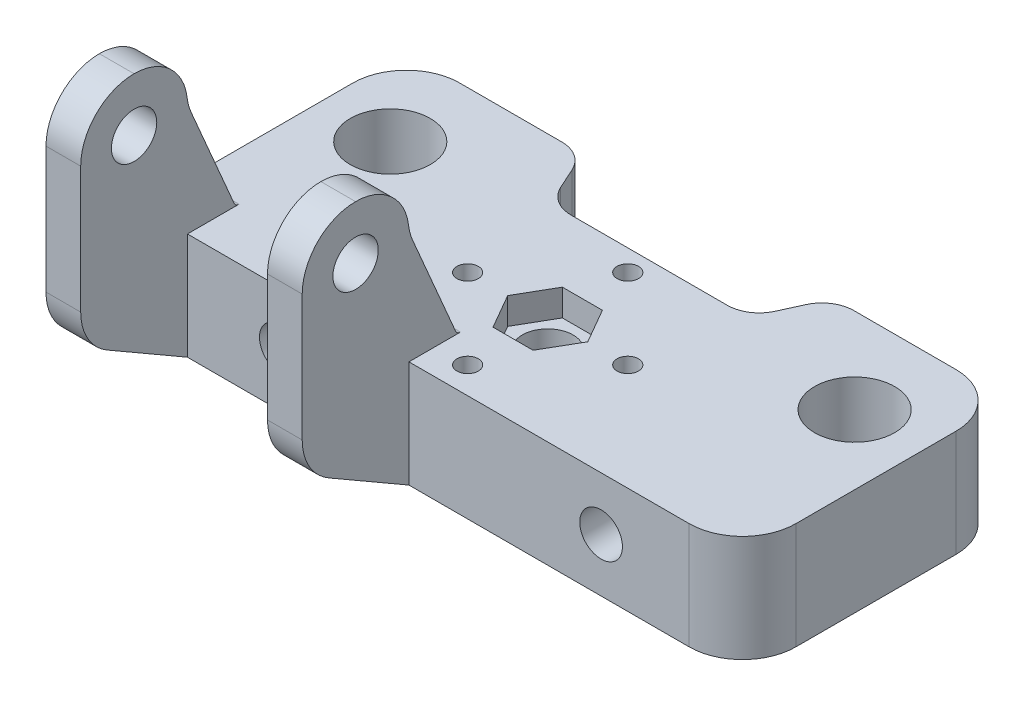
SolidWorks part; units mm, degrees
material "ABS PC"
ref_plane "Front Plane" through (0, 0, 0) normal (0, 0, 1) x (1, 0, 0)
ref_plane "Top Plane" through (0, 0, 0) normal (0, 1, 0) x (1, 0, 0)
ref_plane "Right Plane" through (0, 0, 0) normal (1, 0, 0) x (0, 0, -1)
sketch "Sketch1" plane through (0, 0, 0) normal (0, 1, 0) x (1, 0, 0)
  line L0 (56.5, 0) -> (-56.5, 0)
  line L1 (56.5, 0) -> (56.5, 50)
  line L2 (-56.5, 0) -> (-56.5, 50)
  line L3 (56.5, 50) -> (-56.5, 50)
  dimension "D1" = 113
  dimension "D2" = 50
extrude "Boss-Extrude1" add sketch "Sketch1" along normal blind 20
sketch "Sketch2" plane through (0, 20, 0) normal (0, 1, 0) x (1, 0, 0)
  line L1 (56.5, 0) -> (56.5, 50) construction
  line L3 (56.5, 50) -> (-56.5, 50) construction
  circle A0 centre (-43.5, 34) radius 7.5
  circle A1 centre (43.5, 34) radius 7.5
  circle A2 centre (0, 20) radius 4.75
  circle A3 centre (15, 20) radius 2
  circle A4 centre (-15, 20) radius 2
  circle A5 centre (0, 35) radius 2
  circle A6 centre (0, 5) radius 2
  dimension "D2" = 56.5
  dimension "D3" = 30
  dimension "D5" = 15
  dimension "D6" = 15
  dimension "D1" = 43.5
  dimension "D4" = 43.5
  dimension "D7" = 14
  dimension "D8" = 9.5
  dimension "D9" = 15
  dimension "D10" = 15
  dimension "D11" = 4
  dimension "D12" = 15
  dimension "D13" = 15
extrude "Cut-Extrude1" cut sketch "Sketch2" against normal through all
sketch "Sketch3" plane through (0, 20, 0) normal (0, 1, 0) x (1, 0, 0)
  line L1 (-3.75, 13.5048) -> (3.75, 13.5048)
  line L2 (3.75, 13.5048) -> (7.5, 20)
  line L3 (7.5, 20) -> (3.75, 26.4952)
  line L4 (3.75, 26.4952) -> (-3.75, 26.4952)
  line L5 (-3.75, 26.4952) -> (-7.5, 20)
  line L6 (-7.5, 20) -> (-3.75, 13.5048)
  circle A0 centre (0, 20) radius 6.4952 construction
  circle A1 centre (0, 20) radius 4.75 construction
  dimension "D1" = 15
extrude "Cut-Extrude2" cut sketch "Sketch3" against normal blind 5
sketch "Sketch5" plane through (0, 0, -50) normal (0, 0, -1) x (-1, 0, 0)
  line L3 (-56.5, 20) -> (-56.5, 0) construction
  line L4 (-56.5, 0) -> (56.5, 0) construction
  circle A0 centre (30, 10) radius 4
  circle A1 centre (-30, 10) radius 4
  dimension "D1" = 8
  dimension "D2" = 60
  dimension "D3" = 26.5
  dimension "D4" = 10
extrude "Cut-Extrude4" cut sketch "Sketch5" against normal through all
sketch "Sketch12" plane through (0, 20, 0) normal (0, 1, 0) x (1, 0, 0)
  line L4 (23.5, 50) -> (18.5, 39)
  line L5 (56.5, 50) -> (-56.5, 50) construction
  line L6 (18.5, 39) -> (-18.5, 39)
  line L7 (-18.5, 39) -> (-23.5, 50)
  line L8 (-23.5, 50) -> (23.5, 50)
  dimension "D2" = 11
  dimension "D3" = 33
  dimension "D4" = 33
  dimension "D5" = 5
  dimension "D6" = 5
extrude "Cut-Extrude6" cut sketch "Sketch12" against normal through all
fillet "Fillet5" radius 6 4 edges at (-23.5, 10, -50) (23.5, 10, -50) (-18.5, 10, -39) (18.5, 10, -39)
sketch "Sketch13" plane through (0, 0, 0) normal (0, 0, 1) x (1, 0, 0)
  line L0 (-47.5, 0) -> (-47.5, 51)
  line L1 (-47.5, 0) -> (-54, 0)
  line L2 (-47.5, 51) -> (-54, 51)
  line L3 (-54, 0) -> (-54, 51)
  line L4 (-56.5, 0) -> (56.5, 0) construction
  line L5 (-12.5, 0) -> (-6, 0)
  line L6 (-12.5, 0) -> (-12.5, 51)
  line L7 (-6, 0) -> (-6, 51)
  line L8 (-12.5, 51) -> (-6, 51)
  circle A1 centre (-30, 10) radius 4 construction
  dimension "D3" = 17.5
  dimension "D4" = 17.5
  dimension "D1" = 51
  dimension "D2" = 6.5
extrude "Boss-Extrude2" add sketch "Sketch13" along normal blind 20
hole_wizard "Ø8.5 (8.5) Diameter Hole1" positions "Sketch15" profile "Sketch14" hole size "Ø8.5" standard "Ansi Metric" end condition through all
sketch "Sketch15" plane through (-6, 0, 0) normal (1, 0, 0) x (0, 0, -1)
  line L0 (0, 20) -> (0, 51) construction
  point P0 (-10, 41)
  dimension "D1" = 10
  dimension "D2" = 21
sketch "Sketch14" plane through (-6, 41, 10) normal (0, 1, 0) x (0, 0, -1)
  line L0 (0, 0) -> (0, 50.5)
  line L1 (0, 50.5) -> (4.25, 50.5)
  line L2 (4.25, 50.5) -> (4.25, 0)
  line L5 (4.25, 0) -> (0, 0)
  line L11 (0, -6.35) -> (0, 107.95) construction
  dimension "Thru Hole Dia." = 8.5
  dimension "Thru Hole Depth" = 50.5
sketch "Sketch16" plane through (-6, 0, 0) normal (1, 0, 0) x (0, 0, -1)
  line L0 (0, 0) -> (-20, 0)
  line L1 (-20, 0) -> (-20, 11.547)
  line L2 (-20, 0) -> (-20, 51) construction
  line L3 (-20, 11.547) -> (0, 0)
  dimension "D1" = 30
extrude "Cut-Extrude7" cut sketch "Sketch16" against normal through all
fillet "Fillet6" radius 10 2 edges at (-50.75, 11.547, 20) (-9.25, 11.547, 20)
fillet "Fillet7" radius 10 4 edges at (-9.25, 51, 0) (-9.25, 51, 20) (-50.75, 51, 20) (-50.75, 51, 0)
sketch "Sketch18" plane through (-54, 0, 0) normal (-1, 0, 0) x (0, 0, 1)
  line L0 (0, 41) -> (0, 20)
  line L1 (0, 20) -> (-9, 20)
  line L2 (-9, 20) -> (0, 41)
  dimension "D1" = 9
extrude "Boss-Extrude3" add sketch "Sketch18" against normal blind 6.5
fillet "Fillet8" radius 10 1 edges at (-50.75, 41, 0)
sketch "Sketch19" plane through (-6, 0, 0) normal (1, 0, 0) x (0, 0, -1)
  line L0 (0, 41) -> (0, 20)
  line L1 (0, 20) -> (9, 20)
  line L2 (9, 20) -> (0, 41)
  dimension "D1" = 9
extrude "Boss-Extrude4" add sketch "Sketch19" against normal blind 6.5
fillet "Fillet9" radius 10 1 edges at (-9.25, 41, 0)
fillet "Fillet10" radius 1 2 edges at (-9.25, 20, -9) (-50.75, 20, -9)
fillet "Fillet11" radius 10 4 edges at (-56.5, 10, 0) (-56.5, 10, -50) (56.5, 10, -50) (56.5, 10, 0)
